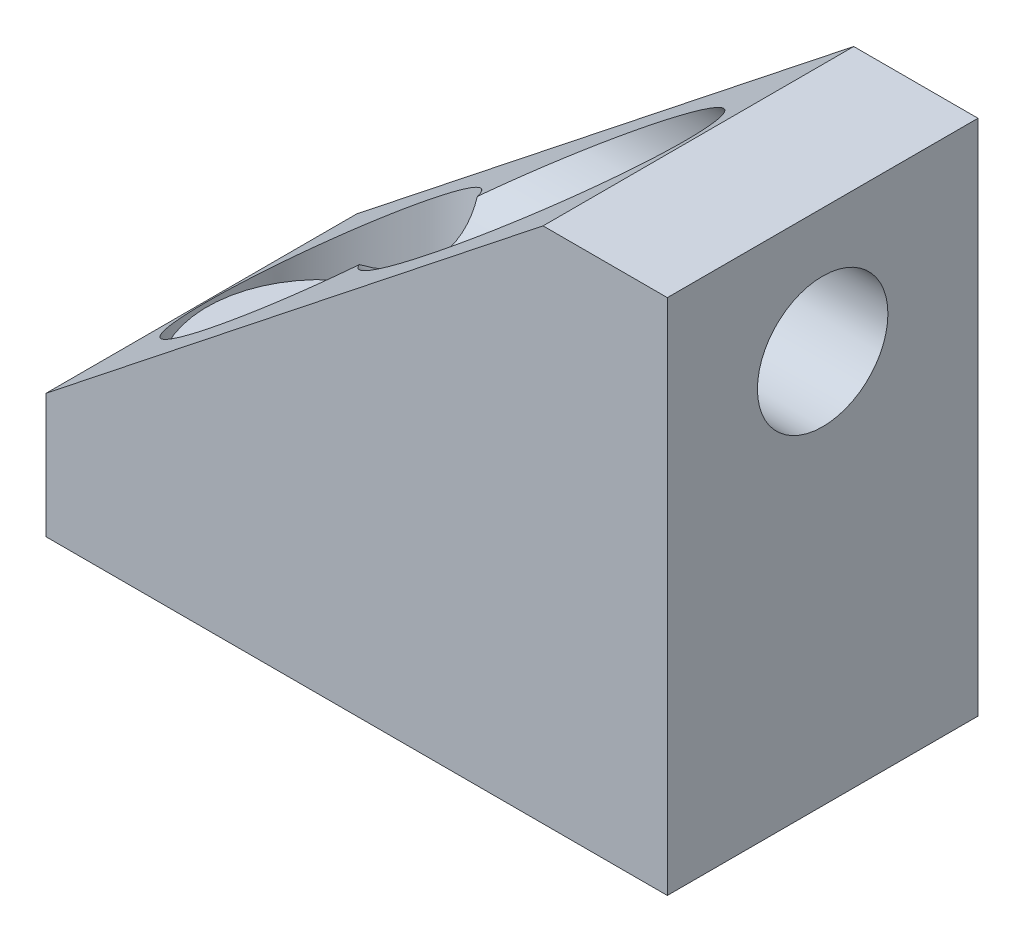
SolidWorks part; units mm, degrees
ref_plane "Front Plane" through (0, 0, 0) normal (0, 0, 1) x (1, 0, 0)
ref_plane "Top Plane" through (0, 0, 0) normal (0, 1, 0) x (1, 0, 0)
ref_plane "Right Plane" through (0, 0, 0) normal (1, 0, 0) x (0, 0, -1)
sketch "Sketch3" plane through (0, 0, 0) normal (0, 0, 1) x (1, 0, 0)
  line L0 (8.3468, 0) -> (38.3468, 0)
  line L1 (55, 0) -> (-55, 0) construction
  line L2 (38.3468, 0) -> (38.3468, 25)
  line L4 (8.3468, 0) -> (8.3468, 6)
  line L6 (38.3468, 25) -> (32.3468, 25)
  line L8 (8.3468, 6) -> (32.3468, 25)
  dimension "D1" = 30
  dimension "D2" = 25
  dimension "D3" = 6
  dimension "D4" = 6
extrude "Boss-Extrude2" add sketch "Sketch3" along normal blind 15 contours L4 | L2 L0 region at (26.4043, 9.8065, 0)
ref_plane "Plane1" through (0, 20, 0) normal (0, 1, 0) x (1, 0, 0)
sketch "Sketch4" plane through (0, 20, 0) normal (0, 1, 0) x (1, 0, 0)
  line L1 (38.3468, -15) -> (38.3468, 0) construction
  line L2 (-55, 0) -> (55, 0) construction
  circle A0 centre (14.1208, -7.5) radius 3.15
  circle A1 centre (14.1208, -7.5) radius 5.5
  dimension "D1" = 6.3
  dimension "D2" = 11
  dimension "D3" = 24.226
  dimension "D4" = 7.5
extrude "Cut-Extrude1" cut sketch "Sketch4" against normal through all contours A0 region at (14.1208, 20, 7.5)
extrude "Cut-Extrude2" cut sketch "Sketch4<3>" against normal blind 14
sketch "Sketch4<3>" plane through (0, 20, 0) normal (0, 1, 0) x (1, 0, 0) same geometry as "Sketch4"
sketch "Sketch6" plane through (0, 0, 0) normal (1, 0, 0) x (0, 0, -1)
  line L1 (55, 0) -> (-55, 0) construction
  line L2 (-15, 0) -> (-15, 25) construction
  circle A0 centre (-7.5, 19) radius 3.15
  circle A1 centre (-7.5, 19) radius 5.5
  dimension "D1" = 6.3
  dimension "D2" = 11
  dimension "D3" = 19
  dimension "D4" = 7.5
extrude "Cut-Extrude3" cut sketch "Sketch6" along normal through all contours A0 region at (0, 19, 7.5)
extrude "Cut-Extrude4" cut sketch "Sketch6<3>" along normal offset from surface (32.3468 mm away) 6 up to face at (38.3468, 19, 4.35)
sketch "Sketch6<3>" plane through (0, 0, 0) normal (1, 0, 0) x (0, 0, -1) same geometry as "Sketch6"
